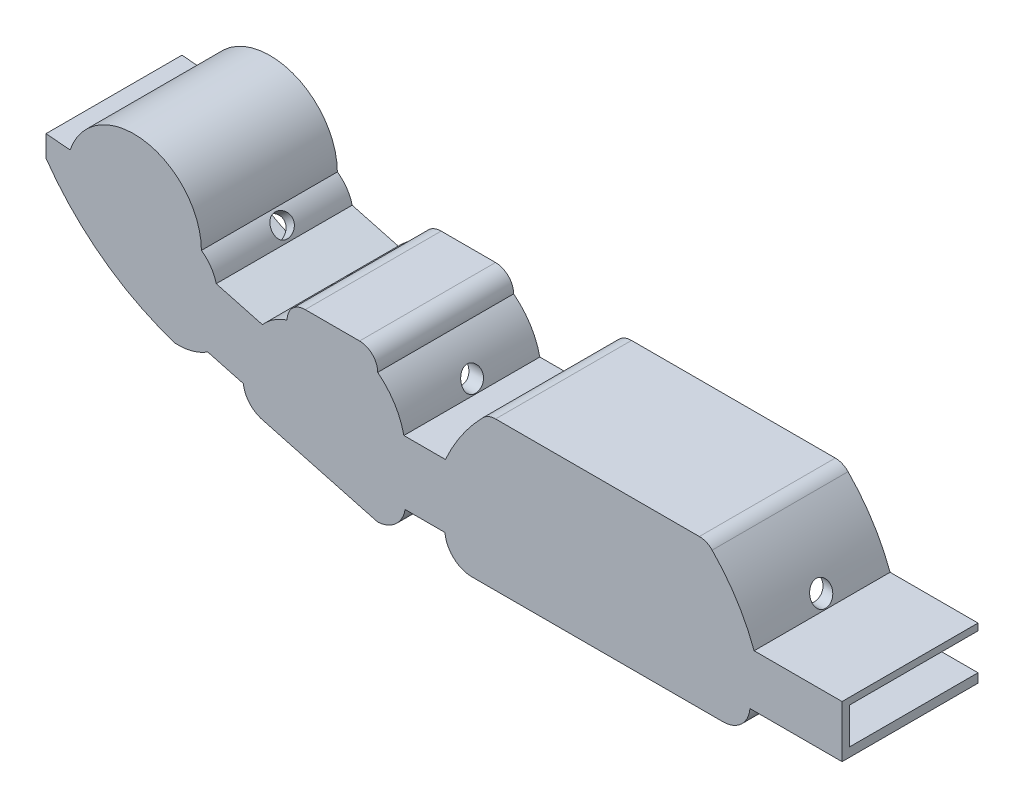
SolidWorks part; units mm, degrees
ref_plane "Front Plane" through (0, 0, 0) normal (0, 0, 1) x (1, 0, 0)
ref_plane "Top Plane" through (0, 0, 0) normal (0, 1, 0) x (1, 0, 0)
ref_plane "Right Plane" through (0, 0, 0) normal (1, 0, 0) x (0, 0, -1)
sketch "Sketch1" plane through (0, 0, 0) normal (0, 0, 1) x (1, 0, 0)
  line L23 (-11.1807, 10.652) -> (-11.4807, 9.152)
  line L24 (-11.4807, 9.152) -> (-11.7807, 10.652)
  line L25 (-11.7807, 10.652) -> (-12.4807, 10.652)
  line L36 (-12.4807, 10.652) -> (-12.7807, 9.152)
  line L40 (-12.7807, 9.152) -> (-13.0807, 10.652)
  line L41 (-13.0807, 10.652) -> (-13.7547, 10.652)
  line L47 (-13.7547, 10.652) -> (-14.0547, 9.152)
  line L48 (-14.0547, 9.152) -> (-14.3547, 10.652)
  line L49 (-14.3547, 10.652) -> (-15.0547, 10.652)
  line L50 (-15.0547, 10.652) -> (-15.3547, 9.152)
  line L51 (-15.3547, 9.152) -> (-15.6547, 10.652)
  line L52 (-15.6547, 10.652) -> (-16.3547, 10.652)
  line L53 (-16.3547, 10.652) -> (-16.6547, 9.152)
  line L54 (-16.6547, 9.152) -> (-16.9547, 10.652)
  line L55 (-16.9547, 10.652) -> (-17.6547, 10.652)
  line L56 (-17.6547, 10.652) -> (-17.9547, 9.152)
  line L57 (-17.9547, 9.152) -> (-18.2547, 10.652)
  line L58 (-18.2547, 10.652) -> (-18.9547, 10.652)
  line L59 (-18.9547, 10.652) -> (-19.2547, 9.152)
  line L60 (-19.2547, 9.152) -> (-19.5547, 10.652)
  line L61 (-19.5547, 10.652) -> (-20.2547, 10.652)
  line L62 (-20.2547, 10.652) -> (-20.5547, 9.152)
  line L63 (-20.5547, 9.152) -> (-20.8547, 10.652)
  line L64 (-20.8547, 10.652) -> (-21.5547, 10.652)
  line L65 (-21.5547, 10.652) -> (-21.8547, 9.152)
  line L66 (-21.8547, 9.152) -> (-22.1547, 10.652)
  line L67 (-22.1547, 10.652) -> (-22.8547, 10.652)
  line L68 (-22.8547, 10.652) -> (-23.1547, 9.152)
  line L69 (-23.1547, 9.152) -> (-23.4547, 10.652)
  line L70 (-23.4547, 10.652) -> (-24.1547, 10.652)
  line L71 (-24.1547, 10.652) -> (-24.4547, 9.152)
  line L72 (-24.4547, 9.152) -> (-24.7547, 10.652)
  line L73 (-24.7547, 10.652) -> (-25.4547, 10.652)
  line L74 (-25.4547, 10.652) -> (-25.7547, 9.152)
  line L75 (-25.7547, 9.152) -> (-26.0547, 10.652)
  line L167 (-65.6227, -2.5345) -> (-53.067, -5.904)
  line L170 (-79.6403, 18.0546) -> (-79.9403, 16.9546)
  line L171 (8.2817, 1.895) -> (-3.6348, 1.895)
  line L172 (-10.5067, 10.652) -> (-11.1807, 10.652)
  line L173 (-9.9067, 10.652) -> (-9.3532, 10.652)
  line L175 (-90.0385, 17.2605) -> (-90.3385, 15.3605)
  line L176 (-9.9067, 10.652) -> (-10.2067, 9.152)
  line L177 (-10.2067, 9.152) -> (-10.5067, 10.652)
  line L178 (-95.1809, 13.2035) -> (-95.1809, 13.9397)
  line L179 (-3.7183, -2.905) -> (8.2817, -2.905)
  line L180 (-2.7142, -4.105) -> (9.4817, -4.105)
  line L181 (-59.7303, 10.6765) -> (-60.0303, 9.1765)
  line L183 (9.4817, 2.795) -> (9.4817, -4.105)
  line L184 (8.2817, 1.895) -> (8.2817, -2.905)
  line L185 (-2.1578, 2.795) -> (9.4817, 2.795)
  line L186 (-78.3403, 16.8698) -> (-78.6403, 15.6698)
  line L187 (-95.9224, 15.2117) -> (-92.734, 14.9402)
  line L188 (-59.0303, 10.6765) -> (-59.7303, 10.6765)
  line L189 (-83.5403, 19.5521) -> (-83.8403, 18.4521)
  line L190 (-90.3385, 15.3605) -> (-90.6385, 16.5942)
  line L191 (-93.1375, 12.3801) -> (-94.7953, 13.499)
  line L192 (-56.1563, 9.1765) -> (-56.4563, 10.6765)
  line L193 (-61.3303, 9.1765) -> (-61.6303, 10.6765)
  line L194 (-72.2095, 0.2626) -> (-69.8019, -0.3835)
  line L195 (-50.0895, 3.0893) -> (-42.0895, 3.0893)
  line L196 (-57.7563, 10.6765) -> (-58.4303, 10.6765)
  line L197 (-79.9403, 16.9546) -> (-80.2403, 18.4517)
  line L198 (-60.0303, 9.1765) -> (-60.3303, 10.6765)
  line L199 (-83.8403, 18.4521) -> (-84.1403, 19.592)
  line L200 (-67.2694, 7.634) -> (-73.3819, 9.2744)
  line L201 (-57.4563, 9.1765) -> (-57.7563, 10.6765)
  line L202 (-86.1394, 19.3991) -> (-86.4394, 18.142)
  line L203 (-88.737, 18.3082) -> (-89.037, 16.8082)
  line L204 (-95.1809, 13.9397) -> (-94.7953, 13.499)
  line L205 (-80.9403, 18.8256) -> (-81.2403, 17.8256)
  line L206 (-85.1416, 18.3912) -> (-85.4416, 19.5242)
  line L207 (-75.7574, 2.4572) -> (-67.9168, 0.353)
  line L208 (-91.8834, 9.2598) -> (-95.1809, 13.2035)
  line L209 (-57.1563, 10.6765) -> (-57.4563, 9.1765)
  line L210 (-61.0303, 10.6765) -> (-61.3303, 9.1765)
  line L211 (-42.0938, -2.9107) -> (-50.1202, -2.9107)
  line L212 (-54.4007, 12.1968) -> (-61.6007, 12.1968)
  line L213 (-82.2403, 19.3073) -> (-82.5403, 18.2573)
  line L214 (-89.037, 16.8082) -> (-89.337, 17.8803)
  line L215 (-67.0758, -3.3248) -> (-52.0089, -7.3682)
  line L216 (-60.3303, 10.6765) -> (-61.0303, 10.6765)
  line L217 (-87.7388, 17.6881) -> (-88.0388, 18.7113)
  line L218 (-55.8563, 10.6765) -> (-56.1563, 9.1765)
  line L219 (-77.0403, 14.8519) -> (-77.3403, 12.8519)
  line L220 (-48.5348, 4.2893) -> (-43.0376, 4.2893)
  line L221 (-95.9224, 12.3801) -> (-95.9224, 15.2117)
  line L222 (-82.5403, 18.2573) -> (-82.8403, 19.4479)
  line L223 (-86.4394, 18.142) -> (-86.7394, 19.2394)
  line L224 (-72.2095, 0.2626) -> (-74.5067, 0.8791)
  line L225 (-58.7303, 9.1765) -> (-59.0303, 10.6765)
  line L226 (-78.6403, 15.6698) -> (-78.9403, 17.4819)
  line L227 (-74.6154, 8.363) -> (-66.8888, 6.2894)
  line L228 (-58.4303, 10.6765) -> (-58.7303, 9.1765)
  line L229 (-84.8416, 19.5818) -> (-85.1416, 18.3912)
  line L230 (-87.4388, 18.9881) -> (-87.7388, 17.6881)
  line L231 (-61.7142, 10.6765) -> (-61.6303, 10.6765)
  line L232 (-55.7142, 10.6765) -> (-55.8563, 10.6765)
  line L233 (-77.3403, 12.8519) -> (-77.6403, 15.9493)
  line L234 (-48.3689, -4.1107) -> (-43.0979, -4.1107)
  line L235 (-56.4563, 10.6765) -> (-57.1563, 10.6765)
  line L236 (-81.2403, 17.8256) -> (-81.5403, 19.0797)
  line L237 (-27.3547, 10.652) -> (-28.0547, 10.652)
  line L238 (-29.6547, 9.152) -> (-29.9547, 10.652)
  line L239 (-26.0547, 10.652) -> (-26.7547, 10.652)
  line L240 (-35.8547, 10.652) -> (-36.1547, 9.152)
  line L241 (-28.6547, 10.652) -> (-29.3547, 10.652)
  line L242 (-32.2547, 9.152) -> (-32.5547, 10.652)
  line L243 (-28.0547, 10.652) -> (-28.3547, 9.152)
  line L244 (-29.9547, 10.652) -> (-30.6547, 10.652)
  line L245 (-26.7547, 10.652) -> (-27.0547, 9.152)
  line L246 (-33.2547, 10.652) -> (-33.5547, 9.152)
  line L247 (-33.5547, 9.152) -> (-33.8547, 10.652)
  line L248 (-28.3547, 9.152) -> (-28.6547, 10.652)
  line L249 (-32.5547, 10.652) -> (-33.2547, 10.652)
  line L250 (-31.9547, 10.652) -> (-32.2547, 9.152)
  line L251 (-31.2547, 10.652) -> (-31.9547, 10.652)
  line L252 (-33.8547, 10.652) -> (-34.5547, 10.652)
  line L253 (-35.1547, 10.652) -> (-35.8547, 10.652)
  line L254 (-29.3547, 10.652) -> (-29.6547, 9.152)
  line L255 (-34.5547, 10.652) -> (-34.8547, 9.152)
  line L256 (-30.9547, 9.152) -> (-31.2547, 10.652)
  line L257 (-36.1547, 9.152) -> (-36.4547, 10.652)
  line L258 (-27.0547, 9.152) -> (-27.3547, 10.652)
  line L259 (-30.6547, 10.652) -> (-30.9547, 9.152)
  line L260 (-34.8547, 9.152) -> (-35.1547, 10.652)
  line L261 (-36.3935, 12.2625) -> (-9.4143, 12.2681)
  line L262 (-6.3025, -7.4141) -> (-39.5097, -7.4198)
  line L263 (-39.0658, -6.2198) -> (-6.7463, -6.2141)
  arc A66 (-2.7142, -4.105) -> (-6.3025, -7.4141) centre (-6.3025, -3.8141) cw
  arc A67 (-3.7183, -2.905) -> (-6.7463, -6.2141) centre (-6.7023, -3.2144) cw
  arc A69 (-7.343, 8.6822) -> (-9.3532, 10.652) centre (-10.3911, 7.5822) ccw
  arc A70 (-7.343, 8.6822) -> (-3.6348, 1.895) centre (-11.6135, 1.9424) cw
  arc A71 (-2.1578, 2.795) -> (-7.7202, 11.551) centre (-25.381, -5.8132) ccw
  arc A72 (-9.4143, 12.2681) -> (-7.7202, 11.551) centre (-9.4143, 9.9085) cw
  arc A73 (-91.8834, 9.2598) -> (-79.2597, 0.8122) centre (-71.1369, 26.6067) ccw
  arc A74 (-82.8403, 19.4479) -> (-83.5403, 19.5521) centre (-84.3734, 11.5555) ccw
  arc A75 (-95.9224, 12.3801) -> (-78.8178, -0.2725) centre (-68.514, 31.5446) ccw
  arc A76 (-42.0938, -2.9107) -> (-39.0658, -6.2198) centre (-39.1098, -3.2201) ccw
  arc A77 (-74.5067, 0.8791) -> (-78.8178, -0.2725) centre (-78.4378, 6.9504) cw
  arc A78 (-48.5348, 4.2893) -> (-52.0007, 9.7968) centre (-57.8892, 2.2469) ccw
  arc A79 (-50.0895, 3.0893) -> (-53.7142, 8.6765) centre (-57.9847, 1.9367) ccw
  arc A80 (-90.6385, 16.5942) -> (-92.3281, 12.7229) centre (-84.3734, 11.5555) ccw
  arc A81 (-63.7142, 8.6765) -> (-66.8888, 6.2894) centre (-61.8125, 2.8429) ccw
  arc A82 (-52.0007, 9.7968) -> (-54.4007, 12.1968) centre (-54.4007, 9.7968) ccw
  arc A83 (-38.4648, 8.6765) -> (-42.0895, 3.0893) centre (-34.1943, 1.9367) ccw
  arc A84 (-53.067, -5.904) -> (-50.1202, -2.9107) centre (-53.379, -2.6497) ccw
  arc A85 (-86.7394, 19.2394) -> (-87.4388, 18.9881) centre (-84.3734, 11.5555) ccw
  arc A86 (-36.4547, 10.652) -> (-37.9805, 9.9689) centre (-36.4781, 8.6588) ccw
  arc A87 (-53.7142, 8.6765) -> (-55.7142, 10.6765) centre (-55.7142, 8.6765) ccw
  arc A88 (-61.6007, 12.1968) -> (-64.0007, 9.7968) centre (-61.6007, 9.7968) ccw
  arc A89 (-74.6154, 8.363) -> (-76.3403, 11.2242) centre (-78.6292, 7.8938) ccw
  arc A90 (-43.0376, 4.2893) -> (-38.0877, 11.5453) centre (-20.4269, -5.8188) cw
  arc A91 (-89.337, 17.8803) -> (-90.0385, 17.2605) centre (-84.3734, 11.5555) ccw
  arc A92 (-37.9805, 9.9689) -> (-38.4648, 8.6765) centre (-36.4985, 8.6765) ccw
  arc A93 (-81.5403, 19.0797) -> (-82.2403, 19.3073) centre (-84.3734, 11.5555) ccw
  arc A94 (-92.734, 14.9402) -> (-75.3433, 12.1091) centre (-84.2746, 12.0753) cw
  arc A95 (-92.3281, 12.7229) -> (-93.1375, 12.3801) centre (-85.812, -3.7913) ccw
  arc A96 (-52.0089, -7.3682) -> (-48.3689, -4.1107) centre (-52.2363, -3.4517) ccw
  arc A97 (-76.3403, 11.2242) -> (-77.0403, 14.8519) centre (-84.3734, 11.5555) ccw
  arc A98 (-61.7142, 10.6765) -> (-63.7142, 8.6765) centre (-61.7142, 8.6765) ccw
  arc A99 (-36.3935, 12.2625) -> (-38.0877, 11.5453) centre (-36.3935, 9.9028) ccw
  arc A100 (-64.0007, 9.7968) -> (-67.2694, 7.634) centre (-61.7187, 2.7965) ccw
  arc A101 (-84.1403, 19.592) -> (-84.8416, 19.5818) centre (-84.3734, 11.5555) ccw
  arc A102 (-85.4416, 19.5242) -> (-86.1394, 19.3991) centre (-84.3734, 11.5555) ccw
  arc A103 (-67.9168, 0.353) -> (-65.6227, -2.5345) centre (-65.0435, 0.2807) ccw
  arc A104 (-69.8019, -0.3835) -> (-67.0758, -3.3248) centre (-66.3807, 0.0535) ccw
  arc A105 (-80.2403, 18.4517) -> (-80.9403, 18.8256) centre (-84.3734, 11.5555) ccw
  arc A106 (-88.0388, 18.7113) -> (-88.737, 18.3082) centre (-84.3734, 11.5555) ccw
  arc A107 (-77.6403, 15.9493) -> (-78.3403, 16.8698) centre (-84.3734, 11.5555) ccw
  arc A108 (-43.0979, -4.1107) -> (-39.5097, -7.4198) centre (-39.5097, -3.8198) ccw
  arc A109 (-78.9403, 17.4819) -> (-79.6403, 18.0546) centre (-84.3734, 11.5555) ccw
  arc A110 (-79.2597, 0.8122) -> (-75.7574, 2.4572) centre (-78.4833, 3.71) ccw
  arc A111 (-73.3819, 9.2744) -> (-75.3433, 12.1091) centre (-78.09, 8.1126) ccw
  point P0 (-31.7666, 12.2681)
  point P92 (-21.3666, 12.2681)
  dimension "D46" = 4.0411
  dimension "D47" = 4.8493
  dimension "D48" = 8.9313
  dimension "D49" = 8.0399
  dimension "D6" = 103.4626
  dimension "D7" = 1.2
  dimension "D14" = 12
  dimension "D15" = 1.2
  dimension "D18" = 4.8
  dimension "D19" = 6.9
  dimension "D20" = 11.9164
  dimension "D24" = 6
  dimension "D32" = 6
  dimension "D33" = 1.2
  dimension "D34" = 1.2
  dimension "D35" = 8
  dimension "D36" = 8
  dimension "D37" = 18.0933
  dimension "D38" = 20.0133
  dimension "D39" = 3.6247
  dimension "D40" = 5.6348
  dimension "D41" = 8.0264
  dimension "D42" = 8.1181
  dimension "D43" = 5.271
  dimension "D44" = 5.4973
  dimension "D45" = 6.3288
  dimension "D50" = 3.3409
  dimension "D51" = 3.4471
  dimension "D52" = 5.0053
extrude "Walls" add sketch "Sketch1" along normal blind 16 contours L245 region at (-4.602, -5.658, 0)
sketch "Sketch2" plane through (0, 0, 0) normal (0, 0, -1) x (-1, 0, 0)
  line L178 (95.9224, 15.2117) -> (95.9224, 12.3801)
  line L179 (6.3018, -7.4141) -> (39.5091, -7.4198)
  line L180 (36.3935, 12.2625) -> (9.4143, 12.2681)
  line L181 (48.3689, -4.1107) -> (43.0979, -4.1107)
  line L182 (72.2095, 0.2626) -> (74.5067, 0.8791)
  line L183 (48.5348, 4.2893) -> (43.0376, 4.2893)
  line L184 (67.0758, -3.3248) -> (52.0089, -7.3682)
  line L185 (54.4007, 12.1968) -> (61.6007, 12.1968)
  line L186 (67.2694, 7.634) -> (73.3819, 9.2744)
  line L187 (72.2095, 0.2626) -> (69.8019, -0.3835)
  line L188 (95.9224, 15.2117) -> (92.734, 14.9402)
  line L189 (2.1578, 2.795) -> (-9.4817, 2.795)
  line L190 (-9.4817, 2.795) -> (-9.4817, -4.105)
  line L191 (2.7142, -4.105) -> (-9.4817, -4.105)
  arc A95 (73.3819, 9.2744) -> (75.3433, 12.1091) centre (78.09, 8.1126) cw
  arc A96 (43.0979, -4.1107) -> (39.5091, -7.4198) centre (39.5097, -3.8198) cw
  arc A97 (69.8019, -0.3835) -> (67.0758, -3.3248) centre (66.3807, 0.0535) cw
  arc A98 (64.0007, 9.7968) -> (67.2694, 7.634) centre (61.7187, 2.7965) cw
  arc A99 (36.3935, 12.2625) -> (38.0877, 11.5453) centre (36.3935, 9.9028) cw
  arc A100 (52.0089, -7.3682) -> (48.3689, -4.1107) centre (52.2363, -3.4517) cw
  arc A101 (92.734, 14.9402) -> (75.3433, 12.1091) centre (84.2746, 12.0753) ccw
  arc A102 (43.0376, 4.2893) -> (38.0877, 11.5453) centre (20.4269, -5.8188) ccw
  arc A103 (61.6007, 12.1968) -> (64.0007, 9.7968) centre (61.6007, 9.7968) cw
  arc A104 (52.0007, 9.7968) -> (54.4007, 12.1968) centre (54.4007, 9.7968) cw
  arc A105 (48.5348, 4.2893) -> (52.0007, 9.7968) centre (57.8892, 2.2469) cw
  arc A106 (74.5067, 0.8791) -> (78.8178, -0.2725) centre (78.4378, 6.9504) ccw
  arc A107 (95.9224, 12.3801) -> (78.8178, -0.2725) centre (68.514, 31.5446) cw
  arc A108 (9.4143, 12.2681) -> (7.7202, 11.551) centre (9.4143, 9.9085) ccw
  arc A109 (2.1578, 2.795) -> (7.7202, 11.551) centre (25.381, -5.8132) cw
  arc A110 (2.7142, -4.105) -> (6.3018, -7.4141) centre (6.3025, -3.8141) ccw
  point P93 (21.3666, 12.2681)
  point P96 (31.7666, 12.2681)
extrude "Base" add sketch "Sketch2" along normal blind 1
sketch "Sketch3" [suppressed] plane through (0, 0, 0) normal (0, 0, 1) x (1, 0, 0)
  line L4 (-65.1711, 5.3832) -> (-63.3958, 4.9067) construction
  line L5 (-84.8697, 19.5134) -> (-85.1843, 17.3997) construction
  line L6 (-51.77, 3.095) -> (-68.5693, 3.095) construction
  line L7 (-68.5693, 6.2951) -> (-68.5693, 3.095) construction
  line L8 (-51.77, 3.095) -> (-54.6697, 3.095) construction
  line L9 (-68.5693, 6.2951) -> (-65.1711, 5.3832) construction
  line L10 (-56.4697, 3.095) -> (-54.6697, 3.095) construction
  line L11 (-80.595, 9.5224) -> (-82.2789, 9.9743)
  line L12 (-80.595, 9.5224) -> (-76.2959, 8.3687) construction
  line L13 (-91.8537, 12.2226) -> (-90.116, 11.8146)
  line L14 (-82.2789, 9.9743) -> (-90.116, 11.8146) construction
  line L15 (-40.77, 3.095) -> (-37.27, 3.095) construction
  line L16 (-3.6422, 1.595) -> (-7.1422, 1.595) construction
  line L17 (-40.77, 3.095) -> (-3.7183, 3.095) construction
  line L18 (-22.2442, 8.652) -> (-22.2442, 3.095) construction
  line L19 (-22.8547, 10.652) -> (-22.1547, 10.652) construction
  line L20 (-22.2442, 10.652) -> (-22.2442, 8.652) construction
  line L21 (-37.27, 3.095) -> (-34.1769, 3.095) construction
  line L22 (-11.7175, 3.095) -> (-7.1422, 1.595) construction
  arc A1 (-82.2789, 9.9743) -> (-90.116, 11.8146) centre (-86.0365, 11.58) ccw
  arc A2 (-91.8537, 12.2226) -> (-80.595, 9.5224) centre (-86.0443, 11.6231) cw
  arc A3 (-54.6697, 3.095) -> (-65.1711, 5.3832) centre (-60.1697, 3.095) ccw construction
  arc A4 (-84.5208, 19.4536) -> (-85.2208, 19.5578) centre (-86.0539, 11.5612) ccw construction
  arc A5 (-56.4697, 3.095) -> (-63.3958, 4.9067) centre (-60.1697, 3.095) ccw construction
  arc A6 (-3.6422, 1.595) -> (-7.343, 8.6822) centre (-11.6135, 1.9424) ccw construction
  arc A7 (-7.1422, 1.595) -> (-37.27, 3.095) centre (-22.9472, -12.5401) ccw construction
  arc A8 (-11.7175, 3.095) -> (-34.1769, 3.095) centre (-22.9472, -12.5401) ccw construction
  dimension "D1" = 11
  dimension "D2" = 2.137
  dimension "D3" = 7.4
  dimension "D8" = 38.5
  dimension "D4" = 3.5184
  dimension "D5" = 3.5
  dimension "D6" = 3.5
  dimension "D7" = 2
sketch "Sketch4" [suppressed] plane through (0, 0, 16) normal (0, 0, 1) x (1, 0, 0)
  line L7 (-69.5947, 0.3005) -> (-71.4824, -0.3779)
  line L10 (-71.4824, -0.3779) -> (-76.1872, 0.8847)
  line L11 (-76.1872, 0.8847) -> (-77.6773, 2.0433)
  line L12 (-40.77, 3.095) -> (-41.1043, 4.1128)
  line L13 (-41.1043, 4.1128) -> (-49.5364, 4.1128)
  line L16 (-67.7226, 6.3478) -> (-68.9499, 7.6397)
  line L17 (-68.9499, 7.6397) -> (-75.0624, 9.2801)
  line L18 (-75.0624, 9.2801) -> (-76.3177, 7.7352)
  line L19 (-49.5364, 4.1128) -> (-51.77, 3.095)
  line L20 (-40.7743, -2.905) -> (-41.0926, -4.1129)
  line L21 (-41.0926, -4.1129) -> (-49.3636, -4.1129)
  line L22 (-49.3636, -4.1129) -> (-51.8007, -2.905)
  arc A0 (-67.7226, 6.3478) -> (-76.3177, 7.7352) centre (-69.7742, 20.955) cw
  arc A1 (-69.5947, 0.3005) -> (-77.6773, 2.0433) centre (-76.3689, -11.5028) ccw
  arc A2 (-40.7743, -2.905) -> (-51.8007, -2.905) centre (-46.2875, -28.5004) ccw
  arc A3 (-40.77, 3.095) -> (-51.77, 3.095) centre (-46.27, 28.5687) cw
extrude "Joint Width" [suppressed] add sketch "Sketch4" against normal blind 16
ref_plane "SideAnchorPlane" through (0, 0, 2.5) normal (0, 0, 1) x (1, 0, 0)
ref_plane "CentralAnchorPlane" through (0, 0, 13) normal (0, 0, 1) x (1, 0, 0)
sketch "Sketch5" [suppressed] plane through (0, 0, 3) normal (0, 0, 1) x (1, 0, 0)
  line L0 (-76.2959, 8.3687) -> (-68.5693, 6.2951) construction
  line L1 (-76.592, 9.4835) -> (-67.8744, 7.144) construction
  line L2 (-77.4258, 10.7304) -> (-66.9487, 7.9187) construction
  line L3 (-76.592, 9.4835) -> (-88.7757, 4.7797)
  line L4 (-77.4258, 10.7304) -> (-90.1205, 5.8293)
  line L5 (-78.0158, 11.7317) -> (-91.096, 6.6818)
  line L6 (-76.2959, 8.3687) -> (-87.6359, 3.9906)
  line L7 (-78.0158, 11.7317) -> (-77.4258, 10.7304)
  line L9 (-76.592, 9.4835) -> (-76.0479, 8.9395)
  line L10 (-76.0479, 8.9395) -> (-76.2959, 8.3687)
  line L11 (-91.096, 6.6818) -> (-91.096, 6.0024)
  line L12 (-91.096, 6.0024) -> (-90.1205, 5.8293)
  line L13 (-88.7757, 4.7797) -> (-88.5883, 3.9906)
  line L14 (-88.5883, 3.9906) -> (-87.6359, 3.9906)
  arc A0 (-76.2959, 8.3687) -> (-78.0208, 11.2299) centre (-80.3097, 7.8995) ccw construction
  arc A1 (-65.3947, 8.6822) -> (-68.5693, 6.2951) centre (-63.493, 2.8486) ccw construction
  arc A2 (-76.2959, 8.3687) -> (-78.0208, 11.2299) centre (-80.3097, 7.8995) ccw construction
  arc A4 (-93.5639, 9.2655) -> (-80.9402, 0.8179) centre (-72.8174, 26.6123) ccw construction
  arc A5 (-93.5639, 9.2655) -> (-80.9402, 0.8179) centre (-72.8174, 26.6123) ccw construction
  dimension "D1" = 1
  dimension "D2" = 1.5
  dimension "D3" = 1.1466
  dimension "D4" = 1.1466
extrude "Boss-Extrude2" [suppressed] add sketch "Sketch5" along normal blind 1 and the other way blind 1 separate body
sketch "Sketch6" [suppressed] plane through (0, 0, 4) normal (0, 0, 1) x (1, 0, 0)
  line L1 (-87.6359, 3.9906) -> (-76.2959, 8.3687)
  line L4 (-78.0158, 11.7317) -> (-91.096, 6.6818)
  line L5 (-91.096, 6.6818) -> (-91.7792, 6.284)
  line L6 (-91.7792, 6.284) -> (-88.4163, 3.7031)
  line L7 (-88.4163, 3.7031) -> (-87.6359, 3.9906)
  line L8 (-78.0158, 11.7317) -> (-75.9969, 10.8669)
  line L9 (-75.9969, 10.8669) -> (-76.2959, 8.3687)
  arc A0 (-93.5639, 9.2655) -> (-80.9402, 0.8179) centre (-72.8174, 26.6123) ccw construction
extrude "Boss-Extrude4" [suppressed] add sketch "Sketch6" along normal blind 1
sketch "Sketch7" [suppressed] plane through (0, 0, 2) normal (0, 0, -1) x (-1, 0, 0)
  line L0 (87.6359, 3.9906) -> (90.1015, 4.9746)
  line L1 (90.1015, 4.9746) -> (91.096, 6.6818)
  line L2 (91.096, 6.6818) -> (78.0158, 11.7317)
  line L3 (78.0158, 11.7317) -> (76.2959, 10.4542)
  line L4 (76.2959, 10.4542) -> (76.2959, 8.3687)
  line L5 (76.2959, 8.3687) -> (87.6359, 3.9906)
extrude "Boss-Extrude5" [suppressed] add sketch "Sketch7" along normal blind 1
extrude "Boss-Extrude6" [suppressed] add sketch "Sketch3" along normal up to surface (16 mm away)
ref_plane "Plane3" through (-55, 0, 0) normal (1, 0, 0) x (0, 0, -1)
sketch "Sketch14" plane through (-55, 0, 0) normal (1, 0, 0) x (0, 0, -1)
  line L0 (-16, 3.095) -> (1, 3.095) construction
  line L1 (-16, 2.795) -> (1, 2.795) construction
  line L2 (-16, 8.4472) -> (1, 8.4472) construction
  line L4 (-7.5, 8.4472) -> (-7.5, 3.095) construction
  line L6 (-7.5, 5.7711) -> (-16, 5.7711) construction
  line L8 (-16, 8.4472) -> (-16, 3.095) construction
  circle A4 centre (-12.75, 5.7711) radius 1.4 construction
  circle A5 centre (-2.25, 5.7711) radius 1.4 construction
  circle A6 centre (-7.5, 5.7711) radius 1.4
  dimension "D1" = 2.8
  dimension "D2" = 5.25
  dimension "D3" = 0.3
extrude "Cut-Extrude2" cut sketch "Sketch14" along normal up to surface (13.8086 mm away) up to face at (-40.5826, 6.0811, 8)
sketch "Sketch15" plane through (0, 0, 0) normal (1, 0, 0) x (0, 0, -1)
  line L1 (-16, 2.795) -> (1, 2.795) construction
  line L5 (1, 2.795) -> (1, 5.795) construction
  line L7 (1, 5.795) -> (-16, 5.795) construction
  line L8 (-7.5, 5.795) -> (-7.5, 2.795) construction
  line L9 (-16, 11.551) -> (-16, 2.795) construction
  line L10 (-7.5, 4.295) -> (-16, 4.295) construction
  circle A4 centre (-12.75, 4.295) radius 1.4 construction
  circle A5 centre (-2.25, 4.295) radius 1.4 construction
  circle A6 centre (-7.5, 4.295) radius 1.4
  dimension "D2" = 5.25
  dimension "D1" = 2.8
extrude "Cut-Extrude3" cut sketch "Sketch15" against normal up to surface (3.9894 mm away) up to face at (-5.0502, 5.5283, 8)
ref_plane "Plane4" through (-38.5242, -32.3002, 0) normal (0.7663, 0.6425, 0) x (0, 0, -1)
sketch "Sketch16" plane through (-38.5242, -32.3002, 0) normal (0.7663, 0.6425, 0) x (0, 0, -1)
  line L0 (-16, 54.2541) -> (1, 54.2541) construction
  line L1 (-2.5, 57.2123) -> (-13, 57.2123) construction
  line L2 (-13, 55) -> (-13, -55) construction
  line L4 (1, 57.6865) -> (1, 54.2541) construction
  line L6 (-16, 55.9703) -> (1, 55.9703) construction
  line L7 (-7.75, 57.2123) -> (-13, 57.2123) construction
  line L12 (-16, 57.6865) -> (1, 57.6865) construction
  line L13 (-7.5, 57.6865) -> (-7.5, 54.2541) construction
  circle A0 centre (-2.5, 57.2123) radius 1.4 construction
  circle A1 centre (-13, 57.2123) radius 1.4 construction
  circle A2 centre (-12.75, 55.9703) radius 1.4 construction
  circle A3 centre (-2.25, 55.9703) radius 1.4 construction
  circle A4 centre (-7.5, 55.9703) radius 1.4
  dimension "D1" = 2.8
  dimension "D4" = 5.25
  dimension "D5" = 2.8
  dimension "D3" = 5.25
extrude "Cut-Extrude4" cut sketch "Sketch16" against normal up to surface and the other way through all up to face at (-87.8866, 5.3556, 7.5)
ref_plane "Plane5" through (-61.8394, 22.5349, 0) normal (-0.9396, 0.3424, 0) x (0, 0, -1)
sketch "Sketch18" plane through (-61.8394, 22.5349, 0) normal (-0.9396, 0.3424, 0) x (0, 0, -1)
  line L0 (-16, 12.7082) -> (1, 12.7082) construction
  line L1 (-16, 15.8582) -> (-16, 12.7082) construction
  line L5 (-16, 12.7082) -> (1, 12.7082) construction
  line L6 (-7.5, 15.8582) -> (-7.5, 12.7082) construction
  line L14 (-7.5, 14.2832) -> (-16, 14.2832) construction
  circle A2 centre (-12.75, 14.2832) radius 1.4 construction
  circle A3 centre (-2.25, 14.2832) radius 1.4 construction
  circle A4 centre (-7.5, 14.2832) radius 1.4
  dimension "D1" = 2.8
  dimension "D2" = 5.25
  dimension "D3" = 17
  dimension "D4" = 3.15
extrude "Cut-Extrude5" cut sketch "Sketch18" against normal up to surface (1.3127 mm away) up to face at (-65.4008, 7.615, 8)
sketch "Sketch19" plane through (0, 0, 0) normal (0, 0, 1) x (1, 0, 0)
  line L457 (-11.1807, 10.652) -> (-11.4807, 9.152)
  line L460 (-11.4807, 9.152) -> (-11.7807, 10.652)
  line L467 (-11.7807, 10.652) -> (-12.4807, 10.652)
  line L567 (-12.4807, 10.652) -> (-12.7807, 9.152)
  line L568 (-12.7807, 9.152) -> (-13.0807, 10.652)
  line L569 (-13.0807, 10.652) -> (-13.7547, 10.652)
  line L570 (-13.7547, 10.652) -> (-14.0547, 9.152)
  line L571 (-14.0547, 9.152) -> (-14.3547, 10.652)
  line L572 (-14.3547, 10.652) -> (-15.0547, 10.652)
  line L573 (-15.0547, 10.652) -> (-15.3547, 9.152)
  line L574 (-15.3547, 9.152) -> (-15.6547, 10.652)
  line L575 (-15.6547, 10.652) -> (-16.3547, 10.652)
  line L576 (-16.3547, 10.652) -> (-16.6547, 9.152)
  line L577 (-16.6547, 9.152) -> (-16.9547, 10.652)
  line L578 (-16.9547, 10.652) -> (-17.6547, 10.652)
  line L579 (-17.6547, 10.652) -> (-17.9547, 9.152)
  line L580 (-17.9547, 9.152) -> (-18.2547, 10.652)
  line L581 (-18.2547, 10.652) -> (-18.9547, 10.652)
  line L582 (-18.9547, 10.652) -> (-19.2547, 9.152)
  line L583 (-19.2547, 9.152) -> (-19.5547, 10.652)
  line L584 (-19.5547, 10.652) -> (-20.2547, 10.652)
  line L585 (-20.2547, 10.652) -> (-20.5547, 9.152)
  line L586 (-20.5547, 9.152) -> (-20.8547, 10.652)
  line L587 (-20.8547, 10.652) -> (-21.5547, 10.652)
  line L588 (-21.5547, 10.652) -> (-21.8547, 9.152)
  line L589 (-21.8547, 9.152) -> (-22.1547, 10.652)
  line L590 (-22.1547, 10.652) -> (-22.8547, 10.652)
  line L591 (-22.8547, 10.652) -> (-23.1547, 9.152)
  line L592 (-23.1547, 9.152) -> (-23.4547, 10.652)
  line L593 (-23.4547, 10.652) -> (-24.1547, 10.652)
  line L594 (-24.1547, 10.652) -> (-24.4547, 9.152)
  line L595 (-24.4547, 9.152) -> (-24.7547, 10.652)
  line L596 (-24.7547, 10.652) -> (-25.4547, 10.652)
  line L597 (-25.4547, 10.652) -> (-25.7547, 9.152)
  line L598 (-25.7547, 9.152) -> (-26.0547, 10.652)
  line L599 (-65.6227, -2.5345) -> (-53.067, -5.904)
  line L600 (-79.6403, 18.0546) -> (-79.9403, 16.9546)
  line L601 (8.2817, 1.895) -> (-3.6348, 1.895)
  line L602 (-10.5067, 10.652) -> (-11.1807, 10.652)
  line L603 (-9.9067, 10.652) -> (-9.3532, 10.652)
  line L604 (-90.0385, 17.2605) -> (-90.3385, 15.3605)
  line L605 (-9.9067, 10.652) -> (-10.2067, 9.152)
  line L606 (-10.2067, 9.152) -> (-10.5067, 10.652)
  line L607 (-95.1809, 13.2035) -> (-95.1809, 13.9397)
  line L608 (-3.7183, -2.905) -> (8.2817, -2.905)
  line L610 (-59.7303, 10.6765) -> (-60.0303, 9.1765)
  line L612 (8.2817, 1.895) -> (8.2817, -2.905)
  line L614 (-78.3403, 16.8698) -> (-78.6403, 15.6698)
  line L616 (-59.0303, 10.6765) -> (-59.7303, 10.6765)
  line L617 (-83.5403, 19.5521) -> (-83.8403, 18.4521)
  line L618 (-90.3385, 15.3605) -> (-90.6385, 16.5942)
  line L619 (-93.1375, 12.3801) -> (-94.7953, 13.499)
  line L620 (-56.1563, 9.1765) -> (-56.4563, 10.6765)
  line L621 (-61.3303, 9.1765) -> (-61.6303, 10.6765)
  line L623 (-50.0895, 3.0893) -> (-42.0895, 3.0893)
  line L624 (-57.7563, 10.6765) -> (-58.4303, 10.6765)
  line L625 (-79.9403, 16.9546) -> (-80.2403, 18.4517)
  line L626 (-60.0303, 9.1765) -> (-60.3303, 10.6765)
  line L627 (-83.8403, 18.4521) -> (-84.1403, 19.592)
  line L629 (-57.4563, 9.1765) -> (-57.7563, 10.6765)
  line L630 (-86.1394, 19.3991) -> (-86.4394, 18.142)
  line L631 (-88.737, 18.3082) -> (-89.037, 16.8082)
  line L632 (-95.1809, 13.9397) -> (-94.7953, 13.499)
  line L633 (-80.9403, 18.8256) -> (-81.2403, 17.8256)
  line L634 (-85.1416, 18.3912) -> (-85.4416, 19.5242)
  line L635 (-75.7574, 2.4572) -> (-67.9168, 0.353)
  line L636 (-91.8834, 9.2598) -> (-95.1809, 13.2035)
  line L637 (-57.1563, 10.6765) -> (-57.4563, 9.1765)
  line L638 (-61.0303, 10.6765) -> (-61.3303, 9.1765)
  line L639 (-42.0938, -2.9107) -> (-50.1202, -2.9107)
  line L641 (-82.2403, 19.3073) -> (-82.5403, 18.2573)
  line L642 (-89.037, 16.8082) -> (-89.337, 17.8803)
  line L644 (-60.3303, 10.6765) -> (-61.0303, 10.6765)
  line L645 (-87.7388, 17.6881) -> (-88.0388, 18.7113)
  line L646 (-55.8563, 10.6765) -> (-56.1563, 9.1765)
  line L647 (-77.0403, 14.8519) -> (-77.3403, 12.8519)
  line L650 (-82.5403, 18.2573) -> (-82.8403, 19.4479)
  line L651 (-86.4394, 18.142) -> (-86.7394, 19.2394)
  line L653 (-58.7303, 9.1765) -> (-59.0303, 10.6765)
  line L654 (-78.6403, 15.6698) -> (-78.9403, 17.4819)
  line L655 (-74.6154, 8.363) -> (-66.8888, 6.2894)
  line L656 (-58.4303, 10.6765) -> (-58.7303, 9.1765)
  line L657 (-84.8416, 19.5818) -> (-85.1416, 18.3912)
  line L658 (-87.4388, 18.9881) -> (-87.7388, 17.6881)
  line L659 (-61.7142, 10.6765) -> (-61.6303, 10.6765)
  line L660 (-55.7142, 10.6765) -> (-55.8563, 10.6765)
  line L661 (-77.3403, 12.8519) -> (-77.6403, 15.9493)
  line L663 (-56.4563, 10.6765) -> (-57.1563, 10.6765)
  line L664 (-81.2403, 17.8256) -> (-81.5403, 19.0797)
  line L665 (-27.3547, 10.652) -> (-28.0547, 10.652)
  line L666 (-29.6547, 9.152) -> (-29.9547, 10.652)
  line L667 (-26.0547, 10.652) -> (-26.7547, 10.652)
  line L668 (-35.8547, 10.652) -> (-36.1547, 9.152)
  line L669 (-28.6547, 10.652) -> (-29.3547, 10.652)
  line L670 (-32.2547, 9.152) -> (-32.5547, 10.652)
  line L671 (-28.0547, 10.652) -> (-28.3547, 9.152)
  line L672 (-29.9547, 10.652) -> (-30.6547, 10.652)
  line L673 (-26.7547, 10.652) -> (-27.0547, 9.152)
  line L674 (-33.2547, 10.652) -> (-33.5547, 9.152)
  line L675 (-33.5547, 9.152) -> (-33.8547, 10.652)
  line L676 (-28.3547, 9.152) -> (-28.6547, 10.652)
  line L677 (-32.5547, 10.652) -> (-33.2547, 10.652)
  line L678 (-31.9547, 10.652) -> (-32.2547, 9.152)
  line L679 (-31.2547, 10.652) -> (-31.9547, 10.652)
  line L680 (-33.8547, 10.652) -> (-34.5547, 10.652)
  line L681 (-35.1547, 10.652) -> (-35.8547, 10.652)
  line L682 (-29.3547, 10.652) -> (-29.6547, 9.152)
  line L683 (-34.5547, 10.652) -> (-34.8547, 9.152)
  line L684 (-30.9547, 9.152) -> (-31.2547, 10.652)
  line L685 (-36.1547, 9.152) -> (-36.4547, 10.652)
  line L686 (-27.0547, 9.152) -> (-27.3547, 10.652)
  line L687 (-30.6547, 10.652) -> (-30.9547, 9.152)
  line L688 (-34.8547, 9.152) -> (-35.1547, 10.652)
  line L691 (-39.0658, -6.2198) -> (-6.7463, -6.2141)
  arc A206 (-3.7183, -2.905) -> (-6.7463, -6.2141) centre (-6.7023, -3.2144) cw
  arc A207 (-7.343, 8.6822) -> (-9.3532, 10.652) centre (-10.3911, 7.5822) ccw
  arc A208 (-7.343, 8.6822) -> (-3.6348, 1.895) centre (-11.6135, 1.9424) cw
  arc A211 (-91.8834, 9.2598) -> (-79.2597, 0.8122) centre (-71.1369, 26.6067) ccw
  arc A212 (-82.8403, 19.4479) -> (-83.5403, 19.5521) centre (-84.3734, 11.5555) ccw
  arc A214 (-42.0938, -2.9107) -> (-39.0658, -6.2198) centre (-39.1098, -3.2201) ccw
  arc A217 (-50.0895, 3.0893) -> (-53.7142, 8.6765) centre (-57.9847, 1.9367) ccw
  arc A218 (-90.6385, 16.5942) -> (-92.3281, 12.7229) centre (-84.3734, 11.5555) ccw
  arc A219 (-63.7142, 8.6765) -> (-66.8888, 6.2894) centre (-61.8125, 2.8429) ccw
  arc A221 (-38.4648, 8.6765) -> (-42.0895, 3.0893) centre (-34.1943, 1.9367) ccw
  arc A222 (-53.067, -5.904) -> (-50.1202, -2.9107) centre (-53.379, -2.6497) ccw
  arc A223 (-86.7394, 19.2394) -> (-87.4388, 18.9881) centre (-84.3734, 11.5555) ccw
  arc A224 (-36.4547, 10.652) -> (-37.9805, 9.9689) centre (-36.4781, 8.6588) ccw
  arc A225 (-53.7142, 8.6765) -> (-55.7142, 10.6765) centre (-55.7142, 8.6765) ccw
  arc A227 (-74.6154, 8.363) -> (-76.3403, 11.2242) centre (-78.6292, 7.8938) ccw
  arc A229 (-89.337, 17.8803) -> (-90.0385, 17.2605) centre (-84.3734, 11.5555) ccw
  arc A230 (-37.9805, 9.9689) -> (-38.4648, 8.6765) centre (-36.4985, 8.6765) ccw
  arc A231 (-81.5403, 19.0797) -> (-82.2403, 19.3073) centre (-84.3734, 11.5555) ccw
  arc A233 (-92.3281, 12.7229) -> (-93.1375, 12.3801) centre (-85.812, -3.7913) ccw
  arc A235 (-76.3403, 11.2242) -> (-77.0403, 14.8519) centre (-84.3734, 11.5555) ccw
  arc A236 (-61.7142, 10.6765) -> (-63.7142, 8.6765) centre (-61.7142, 8.6765) ccw
  arc A239 (-84.1403, 19.592) -> (-84.8416, 19.5818) centre (-84.3734, 11.5555) ccw
  arc A240 (-85.4416, 19.5242) -> (-86.1394, 19.3991) centre (-84.3734, 11.5555) ccw
  arc A241 (-67.9168, 0.353) -> (-65.6227, -2.5345) centre (-65.0435, 0.2807) ccw
  arc A243 (-80.2403, 18.4517) -> (-80.9403, 18.8256) centre (-84.3734, 11.5555) ccw
  arc A244 (-88.0388, 18.7113) -> (-88.737, 18.3082) centre (-84.3734, 11.5555) ccw
  arc A245 (-77.6403, 15.9493) -> (-78.3403, 16.8698) centre (-84.3734, 11.5555) ccw
  arc A247 (-78.9403, 17.4819) -> (-79.6403, 18.0546) centre (-84.3734, 11.5555) ccw
  arc A248 (-79.2597, 0.8122) -> (-75.7574, 2.4572) centre (-78.4833, 3.71) ccw
  point P2 (-31.7666, 12.2681)
  point P223 (-21.3666, 12.2681)
  dimension "D39" = 8.0264
  dimension "D41" = 8.1181
  dimension "D45" = 4.0411
  dimension "D48" = 8.0399
  dimension "D6" = 4.8
  dimension "D21" = 12
  dimension "D22" = 11.9164
  dimension "D25" = 6
  dimension "D26" = 6
  dimension "D30" = 8
  dimension "D31" = 8
  dimension "D32" = 18.0933
  dimension "D33" = 20.0133
  dimension "D34" = 3.6247
  dimension "D37" = 5.6348
  dimension "D49" = 3.3409
  dimension "D51" = 5.0053
extrude "Cut-Extrude6" cut sketch "Sketch19" against normal up to surface (1 mm away) up to face at (-47.5887, 4.8728, -1)
sketch "Sketch20" plane through (0, 0, 0) normal (0, 0, 1) x (1, 0, 0)
  line L0 (-92.7723, 5.9212) -> (-90.2933, 8.3383)
  line L1 (-89.959, 7.9659) -> (-92.4232, 5.5632)
  line L2 (-90.2933, 8.3383) -> (-89.959, 7.9659)
  line L3 (-92.4232, 5.5632) -> (-92.7723, 5.9212)
  line L4 (-60.5275, -7.0886) -> (-59.44, -3.0361)
  line L5 (-81.0518, 2.0932) -> (-82.0834, -0.6423)
  line L6 (-58.9571, -3.1657) -> (-60.0446, -7.2182)
  line L7 (-60.0446, -7.2182) -> (-60.5275, -7.0886)
  line L8 (-58.9571, -3.1657) -> (-59.44, -3.0361)
  line L9 (-82.0834, -0.6423) -> (-81.6155, -0.8187)
  line L10 (-24.748, -4.1815) -> (-24.248, -4.1815)
  line L11 (-24.748, -4.1815) -> (-24.748, -10.1505)
  line L12 (-24.748, -10.1505) -> (-24.248, -10.1505)
  line L13 (-24.248, -4.1815) -> (-24.248, -10.1505)
  line L14 (-81.6155, -0.8187) -> (-80.584, 1.9167)
  line L15 (-80.584, 1.9167) -> (-81.0518, 2.0932)
  line L16 (-95.1809, 13.2035) -> (-79.2597, 0.8122) construction
  dimension "D1" = 0.5
  dimension "D2" = 0.5
  dimension "D3" = 0.5
  dimension "D4" = 0.5
extrude "Cut-Extrude7" cut sketch "Sketch20" along normal blind 13 from offset 1
sketch "Sketch21" plane through (0, 0, 0) normal (0, 0, 1) x (1, 0, 0)
  line L0 (9.4817, 2.795) -> (9.4817, -4.105) construction
  line L3 (8.2817, -2.905) -> (9.4817, -2.905)
  line L4 (9.4817, 1.895) -> (9.4817, -2.905)
  line L5 (8.2817, -2.905) -> (8.2817, 1.895)
  line L6 (8.2817, 1.895) -> (9.4817, 1.895)
  dimension "D1" = 4.8
extrude "Cut-Extrude8" cut sketch "Sketch21" against normal up to surface and the other way up to surface up to face at (-47.3926, 10.7665, -1) other way up to face at (-47.3926, 10.7665, 16)
ref_plane "Plane6" through (0, 0, 16) normal (0, 0, 1) x (1, 0, 0)
sketch "Sketch22" plane through (0, 0, 16) normal (0, 0, 1) x (1, 0, 0)
  line L185 (-2.7142, -4.105) -> (9.4817, -4.105)
  line L187 (9.4817, 2.795) -> (9.4817, -4.105)
  line L189 (-2.1578, 2.795) -> (9.4817, 2.795)
  line L191 (-95.9224, 15.2117) -> (-92.734, 14.9402)
  line L198 (-72.2095, 0.2626) -> (-69.8019, -0.3835)
  line L204 (-67.2694, 7.634) -> (-73.3819, 9.2744)
  line L216 (-54.4007, 12.1968) -> (-61.6007, 12.1968)
  line L219 (-67.0758, -3.3248) -> (-52.0089, -7.3682)
  line L224 (-48.5348, 4.2893) -> (-43.0376, 4.2893)
  line L228 (-72.2095, 0.2626) -> (-74.5067, 0.8791)
  line L238 (-48.3689, -4.1107) -> (-43.0979, -4.1107)
  line L265 (-36.394, 12.2625) -> (-9.4148, 12.2681)
  line L266 (-6.3018, -7.4141) -> (-39.5091, -7.4198)
  line L268 (-95.9224, 15.2117) -> (-95.9224, 12.3801)
  arc A77 (-2.7142, -4.105) -> (-6.3018, -7.4141) centre (-6.3025, -3.8141) cw
  arc A81 (-2.1578, 2.795) -> (-7.7202, 11.551) centre (-25.381, -5.8132) ccw
  arc A82 (-9.4148, 12.2681) -> (-7.7202, 11.551) centre (-9.4143, 9.9085) cw
  arc A85 (-95.9224, 12.3801) -> (-78.8178, -0.2725) centre (-68.514, 31.5446) ccw
  arc A87 (-74.5067, 0.8791) -> (-78.8178, -0.2725) centre (-78.4378, 6.9504) cw
  arc A88 (-48.5348, 4.2893) -> (-52.0007, 9.7968) centre (-57.8892, 2.2469) ccw
  arc A92 (-52.0007, 9.7968) -> (-54.4007, 12.1968) centre (-54.4007, 9.7968) ccw
  arc A98 (-61.6007, 12.1968) -> (-64.0007, 9.7968) centre (-61.6007, 9.7968) ccw
  arc A100 (-43.0376, 4.2893) -> (-38.0877, 11.5453) centre (-20.4269, -5.8188) cw
  arc A104 (-92.734, 14.9402) -> (-75.3433, 12.1091) centre (-84.2746, 12.0753) cw
  arc A106 (-52.0089, -7.3682) -> (-48.3689, -4.1107) centre (-52.2363, -3.4517) ccw
  arc A109 (-36.394, 12.2625) -> (-38.0877, 11.5453) centre (-36.3935, 9.9028) ccw
  arc A110 (-64.0007, 9.7968) -> (-67.2694, 7.634) centre (-61.7187, 2.7965) ccw
  arc A114 (-69.8019, -0.3835) -> (-67.0758, -3.3248) centre (-66.3807, 0.0535) ccw
  arc A118 (-43.0979, -4.1107) -> (-39.5091, -7.4198) centre (-39.5097, -3.8198) ccw
  arc A121 (-73.3819, 9.2744) -> (-75.3433, 12.1091) centre (-78.09, 8.1126) ccw
  point P0 (-31.7666, 12.2681)
  point P75 (-21.3666, 12.2681)
  dimension "D28" = 5.271
  dimension "D33" = 4.8493
  dimension "D34" = 8.9313
  dimension "D5" = 6.9
  dimension "D29" = 5.4973
  dimension "D31" = 6.3288
  dimension "D37" = 3.4471
extrude "Boss-Extrude7" add sketch "Sketch22" along normal blind 1
